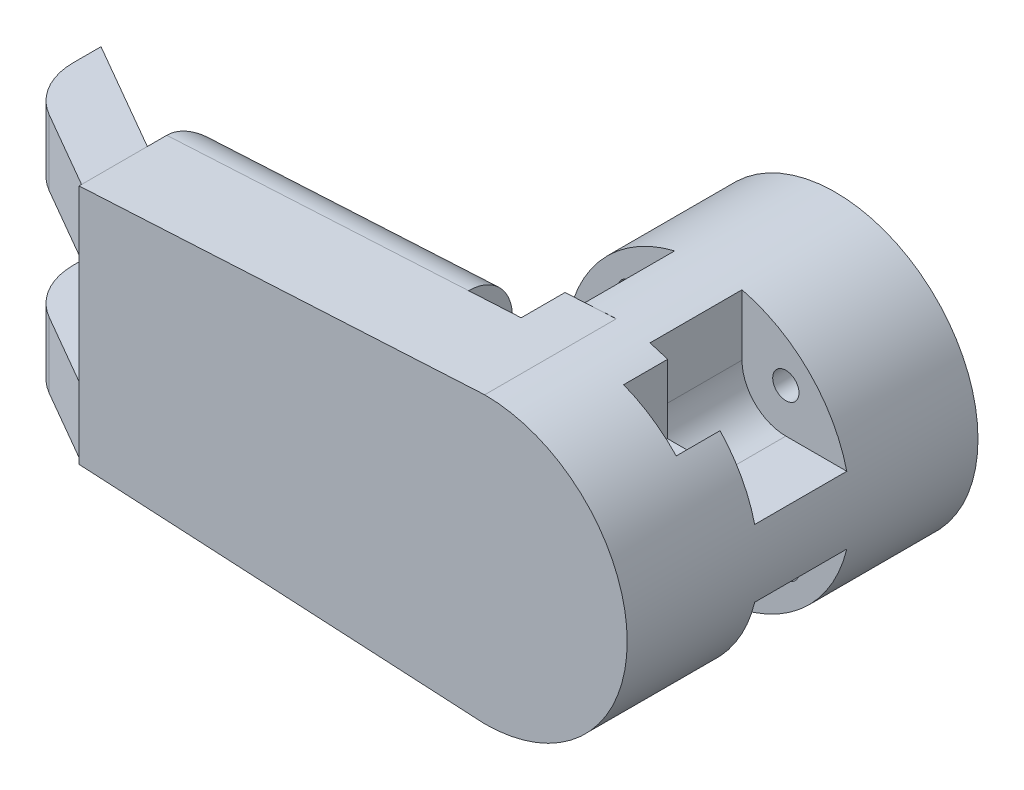
SolidWorks part; units mm, degrees
ref_plane "Front" through (0, 0, 0) normal (0, 0, 1) x (1, 0, 0)
ref_plane "Top" through (0, 0, 0) normal (0, 1, 0) x (1, 0, 0)
ref_plane "Right" through (0, 0, 0) normal (1, 0, 0) x (0, 0, -1)
sketch "Sketch1" plane through (0, 0, 0) normal (0, 0, 1) x (1, 0, 0)
  circle A0 centre (0, 0) radius 32.5
  dimension "D1" = 65
extrude "Boss-Extrude1" add sketch "Sketch1" along normal blind 80
sketch "Sketch2" plane through (0, 0, 80) normal (0, 0, 1) x (1, 0, 0)
  line L1 (-17.68, 17.68) -> (17.68, 17.68) construction
  line L2 (-17.68, 17.68) -> (-17.68, -17.68) construction
  line L3 (-17.68, -17.68) -> (17.68, -17.68) construction
  line L4 (17.68, 17.68) -> (17.68, -17.68) construction
  line L5 (-17.68, 17.68) -> (17.68, -17.68) construction
  line L6 (-17.68, -17.68) -> (17.68, 17.68) construction
  circle A0 centre (17.68, -17.68) radius 3
  circle A1 centre (17.68, 17.68) radius 3
  circle A2 centre (-17.68, 17.68) radius 3
  circle A3 centre (-17.68, -17.68) radius 3
  point P0 (0, 0)
  dimension "D1" = 6
  dimension "D2" = 35.36
  dimension "D3" = 35.36
extrude "Cut-Extrude1" cut sketch "Sketch2" against normal up to next from offset 50 offset against normal yes
ref_plane "Plane1" through (-32.5, 0, 0) normal (-1, 0, 0) x (0, 0, 1)
sketch "Sketch7" plane through (-32.5, 0, 0) normal (-1, 0, 0) x (0, 0, 1)
  line L0 (0, -32.5) -> (80, -32.5) construction
  line L1 (80, 32.5) -> (50, 32.5)
  line L2 (80, 32.5) -> (80, -32.5)
  line L3 (80, -32.5) -> (50, -32.5)
  line L4 (50, 32.5) -> (50, -32.5)
  dimension "D1" = 30
extrude "Boss-Extrude4" add sketch "Sketch7" along normal blind 60 and the other way up to surface other way up to face at (32.5, 0, 80)
sketch "Sketch12" plane through (0, 32.5, 0) normal (0, 1, 0) x (1, 0, 0)
  line L0 (-92.5, -79.4338) -> (-110, -69.3301)
  line L1 (-92.5, -80) -> (-92.5, -50) construction
  line L2 (-117.5, -56.3397) -> (-117.5, -50)
  line L3 (-117.5, -50) -> (-92.5, -64.4338)
  line L4 (-92.5, -64.4338) -> (-92.5, -79.4338)
  line L5 (-92.5, -50) -> (0, -50) construction
  arc A0 (-117.5, -56.3397) -> (-110, -69.3301) centre (-102.5, -56.3397) ccw
  point P8 (0, 0)
  dimension "D3" = 15
  dimension "D1" = 25
  dimension "D2" = 15
  dimension "D4" = 30
extrude "Boss-Extrude5" add sketch "Sketch12" against normal blind 15 from offset 5 offset against normal yes
mirror "Mirror1" about plane through (0, 0, 0) normal (0, 1, 0) of "Boss-Extrude5"
sketch "Sketch10" plane through (0, 0, 0) normal (0, 0, -1) x (-1, 0, 0)
  line L0 (7.68, 17.68) -> (7.68, 31.5795)
  line L1 (17.68, 7.68) -> (31.5795, 7.68)
  arc A0 (7.68, 17.68) -> (17.68, 7.68) centre (17.68, 17.68) ccw
  arc A1 (0, -32.5) -> (0, 32.5) centre (0, 0) ccw construction
  circle A2 centre (0, 0) radius 32.5 construction
  arc A3 (31.5795, 7.68) -> (7.68, 31.5795) centre (0, 0) ccw
  dimension "D1" = 20
extrude "Cut-Extrude2" cut sketch "Sketch10" against normal up to surface (50 mm away) from offset 29 up to face at (-54.375, 0, 50) offset against normal yes
pattern_circular "CirPattern1" count 4 over 360 about axis through (0, 0, 0) along (0, 0, 1) of "Cut-Extrude2"
sketch "Sketch13" plane through (0, 0, 0) normal (0, 0, -1) x (-1, 0, 0)
  line L0 (92.5, 32.5) -> (0, 32.5) construction
  line L1 (11.68, 14.68) -> (23.68, 14.68)
  line L2 (11.68, 14.68) -> (11.68, 32.5)
  line L3 (11.68, 32.5) -> (23.68, 32.5)
  line L4 (23.68, 14.68) -> (23.68, 32.5)
  line L5 (17.68, 17.68) -> (17.68, 14.68) construction
  circle A3 centre (17.68, 17.68) radius 3 construction
  circle A4 centre (17.68, 17.68) radius 3
  point P9 (17.68, 14.68)
  dimension "D1" = 12
extrude "Cut-Extrude3" cut sketch "Sketch13" against normal blind 30 from offset 30 contours L3 L4 L1 L2 offset against normal yes
mirror "Mirror2" about plane through (0, 0, 0) normal (0, 1, 0) of "Cut-Extrude3"
mirror "Mirror3" about plane through (0, 0, 0) normal (1, 0, 0) of "Mirror2"
sketch "Sketch14" plane through (0, 0, 50) normal (0, 0, -1) x (-1, 0, 0)
  line L0 (92.5, 27.5) -> (0, 32.5)
  line L1 (0, 32.5) -> (92.5, 33.5)
  line L2 (92.5, 33.5) -> (92.5, 27.5)
  line L6 (92.5, 32.5) -> (23.68, 32.5) construction
  line L7 (0, 0) -> (148.4689, 0) construction
  line L8 (92.5, -33.5) -> (92.5, -27.5)
  line L9 (0, -32.5) -> (92.5, -33.5)
  line L10 (92.5, -27.5) -> (0, -32.5)
  point P3 (0, 32.5)
  dimension "D1" = 1
extrude "Cut-Extrude4" cut sketch "Sketch14" against normal through all
fillet "Fillet1" radius 10 3 edges at (-92.5, 0, 50) (-58.09, -29.36, 50) (-58.09, 29.36, 50)
